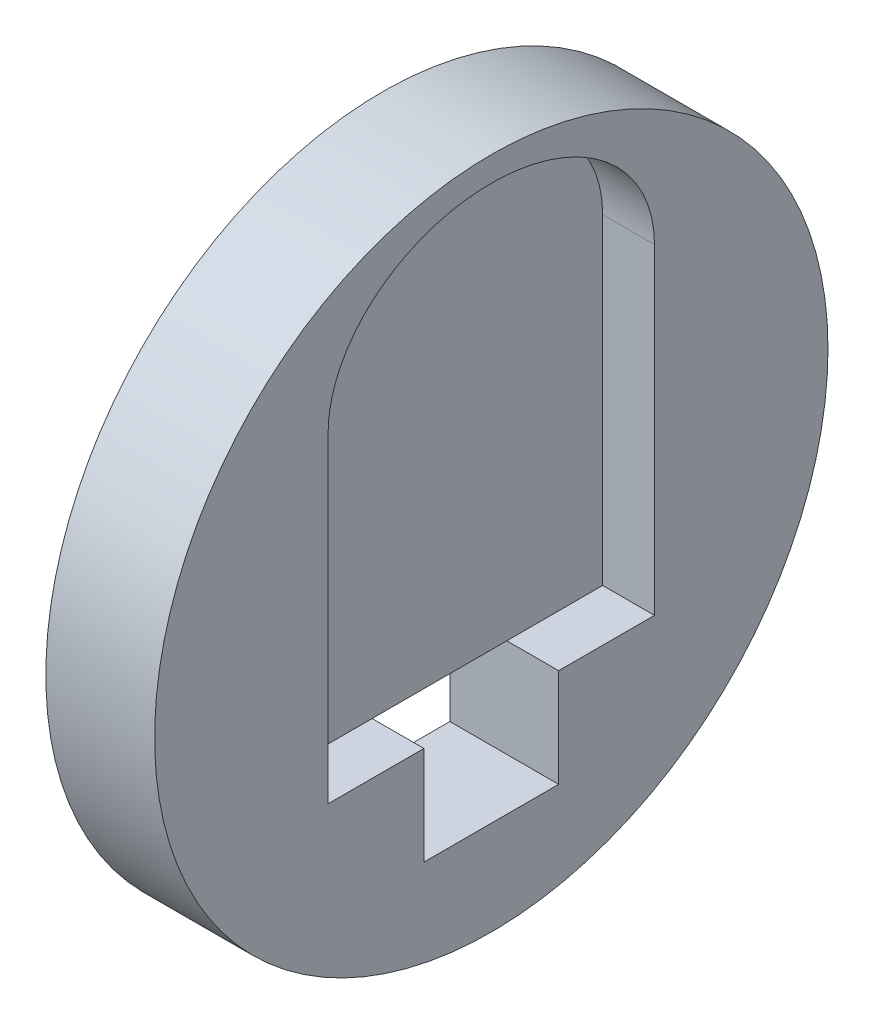
SolidWorks part; units mm, degrees
ref_plane "Front Plane" through (0, 0, 0) normal (0, 0, 1) x (1, 0, 0)
ref_plane "Top Plane" through (0, 0, 0) normal (0, 1, 0) x (1, 0, 0)
ref_plane "Right Plane" through (0, 0, 0) normal (1, 0, 0) x (0, 0, -1)
sketch "Sketch2" plane through (0, 0, 0) normal (1, 0, 0) x (0, 0, -1)
  circle A0 centre (0, 0) radius 32.5
  dimension "D1" = 65
extrude "Boss-Extrude1" add sketch "Sketch2" against normal blind 10.5
sketch "Sketch3" plane through (0, 0, 0) normal (1, 0, 0) x (0, 0, -1)
  line L0 (-15.75, 17.1042) -> (-15.75, -13.8958)
  line L2 (15.75, -13.8958) -> (15.75, 17.1042)
  line L3 (-6.5, -13.8958) -> (-6.5, -18.8958)
  line L4 (-6.5, -18.8958) -> (6.5, -18.8958)
  line L5 (6.5, -18.8958) -> (6.5, -13.8958)
  line L6 (-15.75, -13.8958) -> (-6.5, -13.8958)
  line L7 (6.5, -13.8958) -> (15.75, -13.8958)
  line L8 (-6.5, -13.8958) -> (6.5, -13.8958)
  line L9 (-6.5, -18.8958) -> (-6.5, -23.3958)
  line L10 (-6.5, -23.3958) -> (6.5, -23.3958)
  line L11 (6.5, -23.3958) -> (6.5, -18.8958)
  ellipse E0 centre (0, 17.1042) end of major axis (15.75, 17.1042) minor radius 13
  point P15 (0, 8.5893)
  dimension "D1" = 31.5
  dimension "D6" = 17.1042
  dimension "D2" = 13
  dimension "D3" = 49
  dimension "D4" = 4.5
  dimension "D5" = 13
  dimension "D7" = 31
extrude "Cut-Extrude1" cut sketch "Sketch3" against normal through all contours L10 L11 L4 L9 | L8 L3 L4 L5 region at (0, -16.3958, 0) region at (0, -21.1458, 0)
extrude "Cut-Extrude6" cut sketch "Sketch3<3>" against normal offset from surface (5 mm away) 5.5 contours E0 L0 L6 L8 L7 L2 | E0 region at (0, -3.2984, 0) region at (0, 17.1042, 0) up to face at (-10.5, -18.6458, 0)
sketch "Sketch3<3>" plane through (0, 0, 0) normal (1, 0, 0) x (0, 0, -1) same geometry as "Sketch3"
sketch "Sketch5" plane through (-10.5, 0, 0) normal (-1, 0, 0) x (0, 0, 1)
  line L0 (-1.5, 0) -> (-1.5, -1)
  line L1 (-1.5, -1) -> (1.5, -1)
  line L2 (1.5, -1) -> (1.5, 0)
  line L3 (1.5, -1) -> (5, -1)
  line L4 (5, -1) -> (5, 1.5)
  line L5 (5, 1.5) -> (0, 1.5)
  line L6 (-1, -5) -> (1.5, -5)
  line L7 (-1, -1.5) -> (-1, -5)
  line L8 (1.5, -5) -> (1.5, 0)
  line L9 (-5, 1) -> (-5, -1.5)
  line L10 (-1.5, 1) -> (-5, 1)
  line L11 (-5, -1.5) -> (0, -1.5)
  line L12 (1, 5) -> (-1.5, 5)
  line L13 (1, 1.5) -> (1, 5)
  line L14 (-1.5, 5) -> (-1.5, 0)
  line L15 (0, -1.5) -> (0, -1)
  line L16 (0, -1.5) -> (1.5, -1.5)
  arc A1 (1.5, 0) -> (-1.5, 0) centre (0, 0) ccw
  point P24 (0, 0)
  point P25 (0, 0)
  dimension "D1" = 3
  dimension "D2" = 1
  dimension "D3" = 5
  dimension "D4" = 4
extrude "Extrude-Thin1" add sketch "Sketch5" along normal blind 4 and the other way up to surface (5.5 mm away) separate body thin contours A1 L0 L1 L2 other way up to face at (-5, -1.3958, 0) thin type one direction wall 2
extrude "Boss-Extrude8" add sketch "Sketch5<4>" along normal blind 4 and the other way up to surface (5.5 mm away) separate body contours L11 L1 L0 L14 L10 L9 | A1 L5 L13 L12 L14 | A1 L2 L3 L4 L5 | L16 L11 L7 L6 L8 region at (-10.5, -0.3289, -3.0526) region at (-10.5, 3.141, -0.2978) region at (-10.5, 0.2978, 3.141) region at (-10.5, -3.25, 0.25) other way up to face at (-5, -1.3958, 0)
sketch "Sketch5<4>" plane through (-10.5, 0, 0) normal (-1, 0, 0) x (0, 0, 1) same geometry as "Sketch5"
sketch "Sketch10" plane through (-10.5, 0, 0) normal (-1, 0, 0) x (0, 0, 1)
  line L0 (1.5, -1) -> (1.5, 0) construction
  line L1 (-1.5, 0) -> (-1.5, -1) construction
  line L2 (-1.5, -1) -> (1.5, -1) construction
  line L3 (1.5, -1) -> (1.5, 0)
  line L4 (-1.5, 0) -> (-1.5, -1)
  line L5 (-1.5, -1) -> (1.5, -1)
  arc A0 (1.5, 0) -> (-1.5, 0) centre (0, 0) ccw construction
  arc A1 (1.5, 0) -> (-1.5, 0) centre (0, 0) ccw
extrude "Cut-Extrude5" cut sketch "Sketch10" against normal offset from surface (3.5 mm away) 2 up to face at (-5, -1.3958, 0)
sketch "Sketch8" plane through (-5, 0, 0) normal (-1, 0, 0) x (0, 0, 1)
  point P0 (0, 0)
sketch "Sketch9" plane through (-5, 0, 0) normal (1, 0, 0) x (0, 0, -1)
  point P0 (0, 0)
